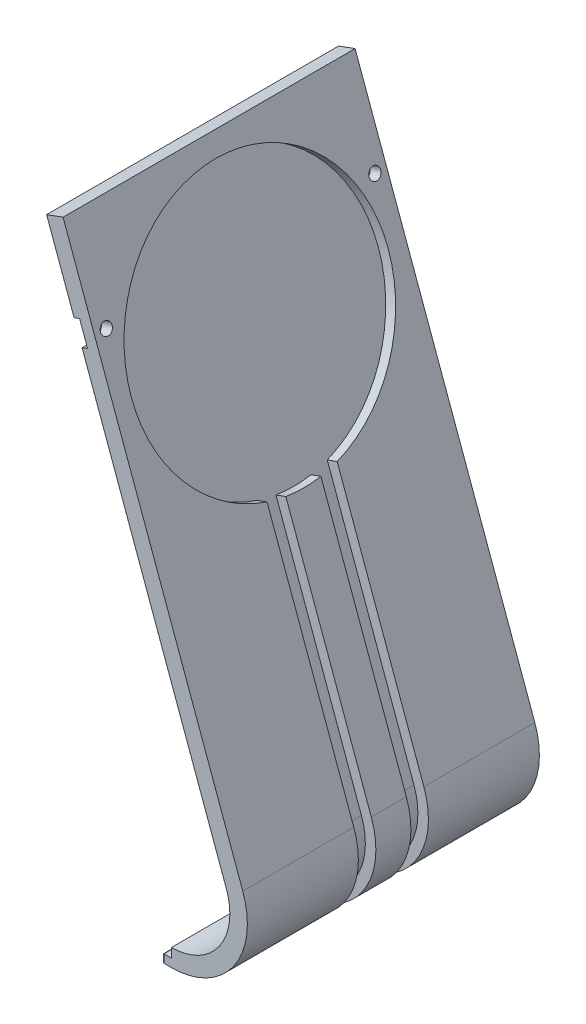
SolidWorks part; units mm, degrees
material "PLA"
ref_plane "前视基准面" through (0, 0, 0) normal (0, 0, 1) x (1, 0, 0)
ref_plane "上视基准面" through (0, 0, 0) normal (0, 1, 0) x (1, 0, 0)
ref_plane "右视基准面" through (0, 0, 0) normal (1, 0, 0) x (0, 0, -1)
other "Configuration Table"
sketch "草图2" plane through (0, 0, 0) normal (0, 0, 1) x (1, 0, 0)
  line L0 (38.2711, 20.4699) -> (5.8755, 109.4762) construction
  line L5 (38.2711, 20.4699) -> (7.4967, 105.022)
  line L10 (28.8742, 7.0497) -> (28.8742, 6.0497) construction
  line L11 (6.4731, 110.7579) -> (8.8224, 111.6129) construction
  arc A0 (28.8742, 7.0497) -> (38.2711, 20.4699) centre (28.8742, 17.0497) ccw
  arc A1 (28.8742, 7.0497) -> (38.2711, 20.4699) centre (28.8742, 17.0497) ccw construction
  dimension "D2" = 10
  dimension "D1" = 5.74
extrude "整体拉伸-薄壁1" add sketch "草图2" along normal mid plane 50 thin thin type one direction wall 3
sketch "草图4" plane through (43.1922, 15.7207, 0) normal (0.9397, 0.342, 0) x (0, 0, -1)
  line L0 (-25, 96.1244) -> (25, 96.1244) construction
  circle A0 centre (0, 70.7244) radius 22
  dimension "D1" = 44
  dimension "D2" = 25.4
extrude "中间圆切除-拉伸1" cut sketch "草图4" against normal blind 1.8
sketch "草图3" plane through (0, 0, 0) normal (0, 0, 1) x (1, 0, 0)
  line L0 (41.0902, 21.4959) -> (10.3157, 106.0481) construction
  line L1 (41.0902, 21.4959) -> (10.3157, 106.0481) construction
  line L2 (28.8742, 4.0497) -> (28.8742, 7.0497) construction
  line L5 (39.3988, 20.8803) -> (24.836, 60.891)
  line L6 (39.3988, 20.8803) -> (8.6243, 105.4325) construction
  line L7 (28.8742, 5.8497) -> (28.8742, 5.8497) construction
  line L9 (24.836, 60.891) -> (26.5275, 61.5067) construction
  line L16 (24.836, 60.891) -> (23.81, 63.7101)
  line L17 (27.0769, 5.9492) -> (18.8326, 8.7934) construction
  arc A0 (28.8742, 7.0497) -> (38.2711, 20.4699) centre (28.8742, 17.0497) ccw construction
  arc A1 (18.8326, 8.7934) -> (41.0902, 21.4959) centre (28.8742, 17.0497) ccw construction
  arc A2 (28.8742, 5.8497) -> (39.3988, 20.8803) centre (28.8742, 17.0497) ccw
  dimension "D2" = 3
  dimension "D1" = 1.8
extrude "线槽切除-拉伸-薄壁1" cut sketch "草图3" against normal blind 3 from offset 6 thin thin type one direction wall 1.8
mirror "镜向1" about plane through (0, 0, 0) normal (0, 0, 1) of "线槽切除-拉伸-薄壁1"
sketch "草图11" plane through (28.8742, 0, 0) normal (-1, 0, 0) x (0, 0, 1)
  line L0 (-25, 4.0497) -> (-25, 7.0497) construction
  line L1 (-25, 5.4497) -> (-6.1, 5.4497)
  line L2 (-25, 5.4497) -> (-25, 4.0497)
  line L3 (-25, 4.0497) -> (-6.1, 4.0497)
  line L4 (-6.1, 5.4497) -> (-6.1, 4.0497)
  line L5 (25, 4.0497) -> (6, 4.0497) construction
  line L6 (6.1, 5.4497) -> (25, 5.4497)
  line L7 (6.1, 5.4497) -> (6.1, 4.0497)
  line L8 (6.1, 4.0497) -> (25, 4.0497)
  line L9 (25, 5.4497) -> (25, 4.0497)
  line L11 (-6, 4.0497) -> (-6, 5.8497) construction
  line L13 (6, 4.0497) -> (6, 5.8497) construction
  line L14 (25, 7.0497) -> (-25, 7.0497) construction
  dimension "D1" = 1.6
  dimension "D2" = 0.1
  dimension "D3" = 0.1
  dimension "D4" = 1.6
extrude "底部卡扣凸台-拉伸3" add sketch "草图11" along normal blind 1.5
fillet "底部卡扣圆角1" radius 0.25 8 edges at (27.3742, 5.4497, 15.55) (27.3742, 4.7497, 25) (27.3742, 4.0497, 15.55) (27.3742, 4.7497, 6.1) (27.3742, 5.4497, -15.55) (27.3742, 4.7497, -6.1) (27.3742, 4.0497, -15.55) (27.3742, 4.7497, -25)
sketch "草图12" plane through (40.3731, 14.6946, 0) normal (-0.9397, -0.342, 0) x (0, 0, 1)
  line L0 (-36.5, 82.3622) -> (36.5, 82.3622) construction
  line L2 (-25, 6.1459) -> (-25, 96.1244) construction
  line L3 (25, 6.1459) -> (25, 96.1244) construction
  circle A0 centre (23, 80.3622) radius 1
  circle A1 centre (-23, 80.3622) radius 1
  dimension "D1" = 2
  dimension "D2" = 2
  dimension "D3" = 2
  dimension "D4" = 2
  dimension "D5" = 2
  dimension "D6" = 2
extrude "螺丝孔" cut sketch "草图12" against normal through all
sketch "草图13" plane through (40.3731, 14.6946, 0) normal (-0.9397, -0.342, 0) x (0, 0, 1)
  line L0 (25, 6.1459) -> (25, 96.1244) construction
  line L1 (23, 82.3622) -> (25, 82.3622)
  line L3 (23, 78.3622) -> (25, 78.3622)
  line L4 (25, 82.3622) -> (25, 78.3622)
  line L5 (-36.5, 82.3622) -> (36.5, 82.3622) construction
  line L6 (0, 96.1244) -> (0, 78.3622) construction
  line L7 (25, 96.1244) -> (-25, 96.1244) construction
  line L8 (-25, 82.3622) -> (-25, 78.3622)
  line L9 (-23, 78.3622) -> (-25, 78.3622)
  line L10 (-23, 82.3622) -> (-25, 82.3622)
  arc A0 (23, 82.3622) -> (23, 78.3622) centre (23, 80.3622) ccw
  arc A1 (-23, 82.3622) -> (-23, 78.3622) centre (-23, 80.3622) cw
  dimension "D1" = 4
extrude "切除-拉伸1" cut sketch "草图13" against normal blind 1
